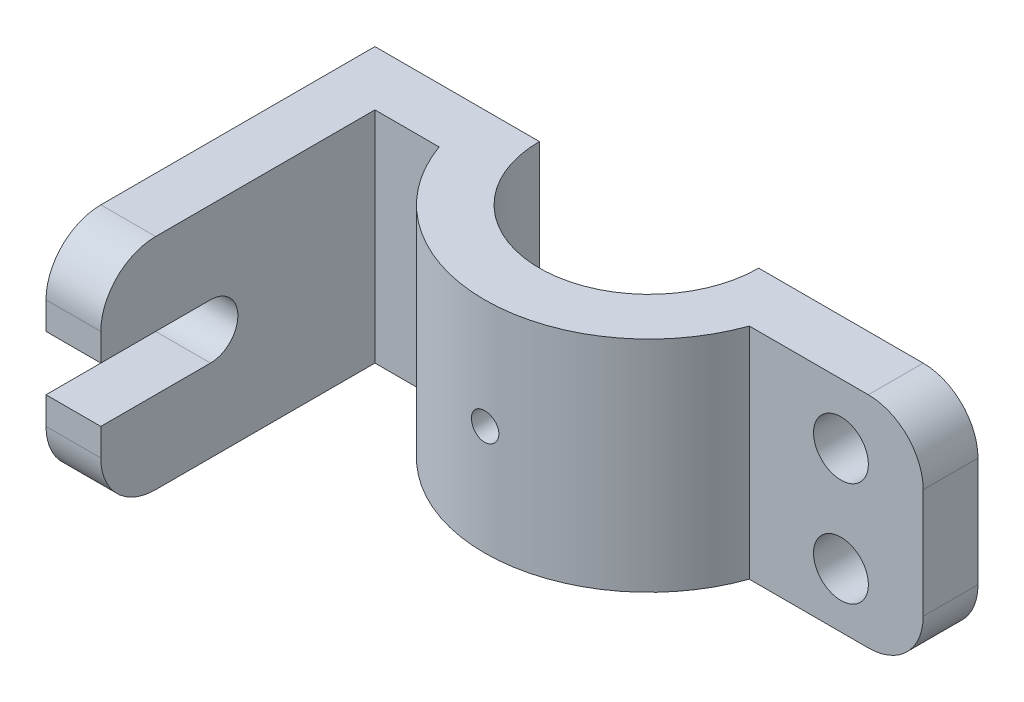
SolidWorks part; units mm, degrees
ref_plane "Alzado" through (0, 0, 0) normal (0, 0, 1) x (1, 0, 0)
ref_plane "Planta" through (0, 0, 0) normal (0, 1, 0) x (1, 0, 0)
ref_plane "Vista lateral" through (0, 0, 0) normal (1, 0, 0) x (0, 0, -1)
sketch "Croquis1" plane through (0, 0, 0) normal (0, 0, 1) x (1, 0, 0)
  line L0 (76.2, 12.7) -> (76.2, -12.7)
  line L1 (-63.5, -25.4) -> (63.5, -25.4)
  line L2 (-63.5, -25.4) -> (-63.5, 25.4)
  line L3 (-63.5, 25.4) -> (63.5, 25.4)
  line L5 (-63.5, -25.4) -> (2.9479, 1.1792) construction
  line L6 (-63.5, 25.4) -> (2.9479, -1.1792) construction
  circle A0 centre (0, 0) radius 3.175
  arc A1 (76.2, 12.7) -> (63.5, 25.4) centre (63.5, 12.7) ccw
  arc A2 (63.5, -25.4) -> (76.2, -12.7) centre (63.5, -12.7) ccw
  circle A3 centre (57.15, 11.455) radius 6.35
  circle A4 centre (57.15, -12.7) radius 6.35
  point P17 (0, 0)
  point P18 (0, 0)
  point P19 (0, 0)
  point P20 (0, 0)
  dimension "D2" = 12.7
  dimension "D3" = 12.7
  dimension "D4" = 12.7
  dimension "D5" = 12.7
  dimension "D10" = 6.35
  dimension "D1" = 25.4
  dimension "D6" = 19.05
  dimension "D7" = 12.7
  dimension "D8" = 50.8
  dimension "D9" = 139.7
  dimension "D11" = 63.5
sketch "Croquis2" plane through (0, 0, 0) normal (0, 1, 0) x (1, 0, 0)
  line L0 (-63.5, 0) -> (-25.4, 0)
  line L1 (-63.5, 0) -> (-63.5, -76.2)
  line L2 (25.4, 0) -> (76.2, 0)
  line L3 (35.921, -12.7) -> (76.2, -12.7)
  line L4 (-50.8, -12.7) -> (-35.921, -12.7)
  line L5 (-50.8, -12.7) -> (-50.8, -76.2)
  line L6 (76.2, 0) -> (76.2, -12.7)
  line L7 (-63.5, -76.2) -> (-50.8, -76.2)
  arc A0 (-25.4, 0) -> (25.4, 0) centre (0, 0) ccw
  arc A1 (-35.921, -12.7) -> (35.921, -12.7) centre (0, 0) ccw
  dimension "D2" = 50.8
  dimension "D1" = 139.7
  dimension "D3" = 76.2
  dimension "D4" = 63.5
  dimension "D5" = 12.7
extrude "Saliente-Extruir1" add sketch "Croquis2" along normal blind 25.4 and the other way blind 25.4
extrude "Cortar-Extruir1" cut sketch "Croquis1" along normal blind 38.1 flip side to cut
sketch "Croquis3" plane through (-50.8, 0, 0) normal (1, 0, 0) x (0, 0, -1)
  line L0 (-76.2, -25.4) -> (-76.2, 25.4) construction
  line L1 (-76.2, 6.35) -> (-50.8, 6.35)
  line L2 (-76.2, 6.35) -> (-76.2, -6.35)
  line L3 (-76.2, -6.35) -> (-50.8, -6.35)
  line L4 (-76.2, -25.4) -> (-12.7, -25.4) construction
  line L5 (-76.2, 25.4) -> (-12.7, 25.4) construction
  line L6 (-63.5, 25.4) -> (-76.2, 25.4)
  line L7 (-76.2, 25.4) -> (-76.2, 12.7)
  line L8 (-76.2, -12.7) -> (-76.2, -25.4)
  line L9 (-76.2, -25.4) -> (-63.5, -25.4)
  arc A0 (-50.8, -6.35) -> (-50.8, 6.35) centre (-50.8, 0) ccw
  arc A1 (-63.5, 25.4) -> (-76.2, 12.7) centre (-63.5, 12.7) ccw
  arc A2 (-76.2, -12.7) -> (-63.5, -25.4) centre (-63.5, -12.7) ccw
  point P21 (-76.2, 20.1013)
  dimension "D1" = 12.7
  dimension "D4" = 12.7
  dimension "D5" = 12.7
  dimension "D2" = 25.4
  dimension "D3" = 19.05
extrude "Cortar-Extruir2" cut sketch "Croquis3" against normal blind 12.7
